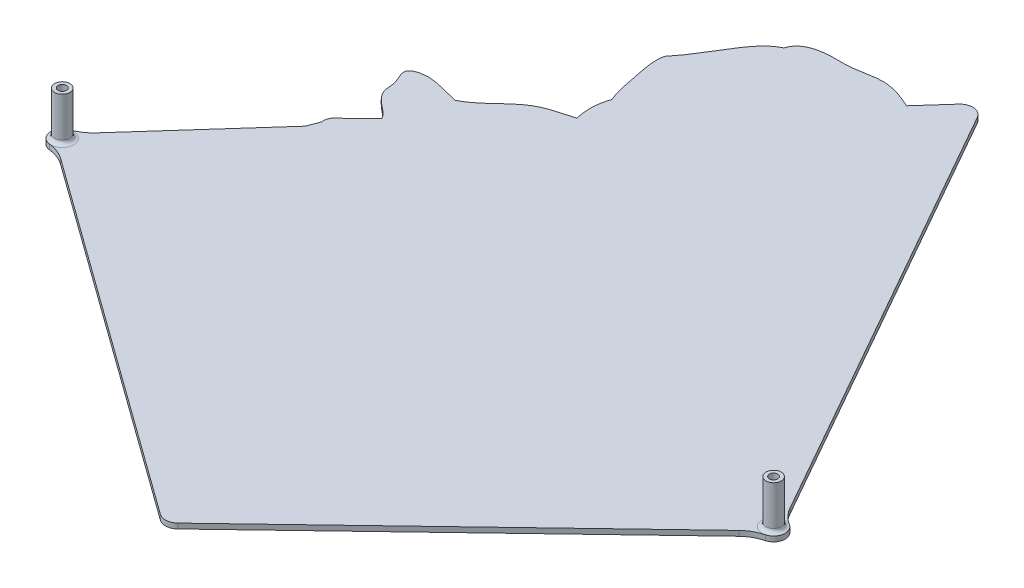
SolidWorks part; units mm, degrees
ref_plane "Front Plane" through (0, 0, 0) normal (0, 0, 1) x (1, 0, 0)
ref_plane "Top Plane" through (0, 0, 0) normal (0, 1, 0) x (1, 0, 0)
ref_plane "Right Plane" through (0, 0, 0) normal (1, 0, 0) x (0, 0, -1)
sketch "Sketch2" plane through (0, 141.5657, 0) normal (0, -1, 0) x (1, 0, 0)
  line L5 (9.9158, 252.3053) -> (48.581, 209.0896)
  line L6 (151.7332, 369.0358) -> (11.6143, 267.9682)
  line L7 (270.3825, 261.2852) -> (158.113, 368.5951)
  line L8 (177.0335, 74.6308) -> (272.9381, 243.9416)
  line L9 (159.2725, 84.5938) -> (168.9553, 73.7627)
  line L15 (9.9158, 252.3053) -> (48.581, 209.0896)
  line L16 (151.7332, 369.0358) -> (11.6143, 267.9682)
  line L17 (270.3825, 261.2852) -> (158.113, 368.5951)
  line L18 (177.0335, 74.6308) -> (272.9381, 243.9416)
  line L19 (159.2725, 84.5938) -> (168.9553, 73.7627)
  arc A9 (48.581, 209.0896) -> (50.3121, 204.4206) centre (186.1941, 257.4563) ccw
  arc A10 (9.9158, 252.3053) -> (3.583, 256.4992) centre (-1.263, 242.3036) ccw
  arc A11 (4.5297, 265.2292) -> (3.583, 256.4992) centre (5.0369, 260.7579) ccw
  arc A12 (4.5297, 265.2292) -> (11.6143, 267.9682) centre (2.8393, 280.1337) ccw
  arc A13 (158.113, 368.5951) -> (151.7332, 369.0358) centre (154.6582, 364.9806) ccw
  arc A14 (270.3825, 261.2852) -> (277.0231, 257.5982) centre (280.7469, 272.1286) ccw
  arc A15 (278.233, 249.3874) -> (277.0231, 257.5982) centre (275.906, 253.239) ccw
  arc A16 (278.233, 249.3874) -> (272.9381, 243.9416) centre (285.9897, 236.5487) ccw
  arc A17 (168.9553, 73.7627) -> (177.0335, 74.6308) centre (172.6829, 77.0951) ccw
  arc A27 (48.581, 209.0896) -> (50.3121, 204.4206) centre (186.1941, 257.4563) ccw
  arc A28 (9.9158, 252.3053) -> (3.583, 256.4992) centre (-1.263, 242.3036) ccw
  arc A29 (4.5297, 265.2292) -> (3.583, 256.4992) centre (5.0369, 260.7579) ccw
  arc A30 (4.5297, 265.2292) -> (11.6143, 267.9682) centre (2.8393, 280.1337) ccw
  arc A31 (158.113, 368.5951) -> (151.7332, 369.0358) centre (154.6582, 364.9806) ccw
  arc A32 (270.3825, 261.2852) -> (277.0231, 257.5982) centre (280.7469, 272.1286) ccw
  arc A33 (278.233, 249.3874) -> (277.0231, 257.5982) centre (275.906, 253.239) ccw
  arc A34 (278.233, 249.3874) -> (272.9381, 243.9416) centre (285.9897, 236.5487) ccw
  arc A35 (168.9553, 73.7627) -> (177.0335, 74.6308) centre (172.6829, 77.0951) ccw
  parabola Q2 (98.9682, 153.2926) -> (99.5004, 140.0615) focus (109.108, 147.0557) apex (98.23, 146.6012)
  parabola Q3 (53.4054, 199.0008) -> (60.976, 191.5788) focus (117.2397, 255.8524) apex (57.8228, 194.5587)
  parabola Q4 (98.9682, 153.2926) -> (99.5004, 140.0615) focus (109.108, 147.0557) apex (98.23, 146.6012)
  parabola Q5 (53.4054, 199.0008) -> (60.976, 191.5788) focus (117.2397, 255.8524) apex (57.8228, 194.5587)
  spline S6 degree 3 poles (2980.7057, -424.9298) (-2880.4178, 1101.2666) (2911.9024, -925.0349) (-2652.0996, 1490.8987) knots -10.131705 -10.131705 -10.131705 -10.131705 11.941134 11.941134 11.941134 11.941134 only from (50.3121, 204.4206) to (53.4054, 199.0008)
  spline S7 degree 3 poles (2545.5152, 1844.1376) (6.2947, 159.0132) (91.6634, 79.7301) (136.3745, 82.9186) (200.6762, 62.3072) (258.0626, 375.5575) (-670.939, -2798.0348) knots -2.235979 -2.235979 -2.235979 -2.235979 0.302256 0.465041 0.71743 4.454806 4.454806 4.454806 4.454806 only from (115.6546, 88.9626) to (159.2725, 84.5938)
  spline S8 degree 3 poles (-2603.0138, -1187.9461) (101.2473, 266.0418) (39.3006, 92.2257) (199.8916, 29.109) (2160.2411, 2281.2724) knots -6.217701 -6.217701 -6.217701 -6.217701 0.601104 5.243144 5.243144 5.243144 5.243144 only from (95.1286, 115.2044) to (115.6546, 88.9626)
  spline S9 degree 3 poles (3058.532, -343.3285) (75.0588, 234.5529) (136.4551, 128.8356) (40.1055, 34.0172) (3078.5584, -183.7583) knots -5.712316 -5.712316 -5.712316 -5.712316 0.482786 6.278016 6.278016 6.278016 6.278016 only from (99.5004, 140.0615) to (95.1286, 115.2044)
  spline S10 degree 3 poles (-1567.0904, -2341.109) (103.3342, 412.4624) (-24.3693, -31.8064) (281.4546, 287.5044) (-1357.121, -2467.5346) knots -4.175993 -4.175993 -4.175993 -4.175993 0.635605 5.166314 5.166314 5.166314 5.166314 only from (69.0332, 171.0536) to (98.9682, 153.2926)
  spline S11 degree 3 poles (-1766.1061, 2570.0287) (172.9879, 136.9571) (73.4504, 212.0462) (51.5071, 181.6794) (51.7464, 177.6623) (50.3461, 174.4095) (48.2598, 169.7911) (55.4446, 167.8741) (111.9527, 179.8669) (251.351, 240.9569) (-2663.5072, -1066.8552) knots -1.992424 -1.992424 -1.992424 -1.992424 0.209803 0.29993 0.400822 0.462711 0.545892 0.679735 0.814877 4.745457 4.745457 4.745457 4.745457 only from (60.976, 191.5788) to (69.0332, 171.0536)
  spline S12 degree 3 poles (50.3121, 204.4206) (49.8157, 202.1257) (51.56, 200.0713) (53.4054, 199.0008) knots 0 0 0 0 1 1 1 1
  spline S13 degree 3 poles (115.6546, 88.9626) (117.1548, 84.0787) (125.5135, 82.1441) (136.3745, 82.9186) (147.179, 79.4553) (155.3838, 82.7877) (159.2725, 84.5938) knots 0 0 0 0 0.302256 0.465041 0.71743 1 1 1 1
  spline S14 degree 3 poles (95.1286, 115.2044) (99.5314, 110.0271) (104.6605, 100.1011) (111.4838, 91.0179) (115.6546, 88.9626) knots 0 0 0 0 0.601104 1 1 1 1
  spline S15 degree 3 poles (99.5004, 140.0615) (97.7554, 136.297) (96.6082, 127.9132) (94.3637, 119.6051) (95.1286, 115.2044) knots 0 0 0 0 0.482786 1 1 1 1
  spline S16 degree 3 poles (69.0332, 171.0536) (75.7897, 167.8566) (82.8631, 156.8368) (94.9037, 154.5658) (98.9682, 153.2926) knots 0 0 0 0 0.635605 1 1 1 1
  spline S17 degree 3 poles (60.976, 191.5788) (59.2764, 188.7875) (55.1822, 186.7652) (51.5071, 181.6794) (51.7464, 177.6623) (50.3461, 174.4095) (48.2598, 169.7911) (55.4446, 167.8741) (61.5549, 169.1709) (66.3898, 170.3925) (69.0332, 171.0536) knots 0 0 0 0 0.209803 0.29993 0.400822 0.462711 0.545892 0.679735 0.814877 1 1 1 1
  dimension "D1" = 0
extrude "Boss-Extrude1" add sketch "Sketch2" against normal blind 2
sketch "Sketch4" plane through (0, 143.5657, 0) normal (0, 1, 0) x (1, 0, 0)
  circle A2 centre (5.0369, -260.7579) radius 3 construction
  circle A3 centre (275.906, -253.239) radius 3 construction
  circle A6 centre (5.0369, -260.7579) radius 3
  circle A7 centre (275.906, -253.239) radius 3
extrude "Boss-Extrude2" add sketch "Sketch4" along normal blind 17
fillet "Fillet1" radius 1.5 2 edges at (275.906, 143.5657, 256.239) (5.0369, 143.5657, 263.7579)
sketch "Sketch5" plane through (0, 141.5657, 0) normal (0, -1, 0) x (1, 0, 0)
  circle A4 centre (275.906, 253.239) radius 1.65
  circle A5 centre (5.0369, 260.7579) radius 1.65
  dimension "D1" = 3.3
  dimension "D2" = 3.3
extrude "Cut-Extrude1" cut sketch "Sketch5" against normal up to next
chamfer "Chamfer1" distance 1 angle 45 2 edges at (275.906, 141.5657, 251.589) (5.0369, 141.5657, 259.1079)
